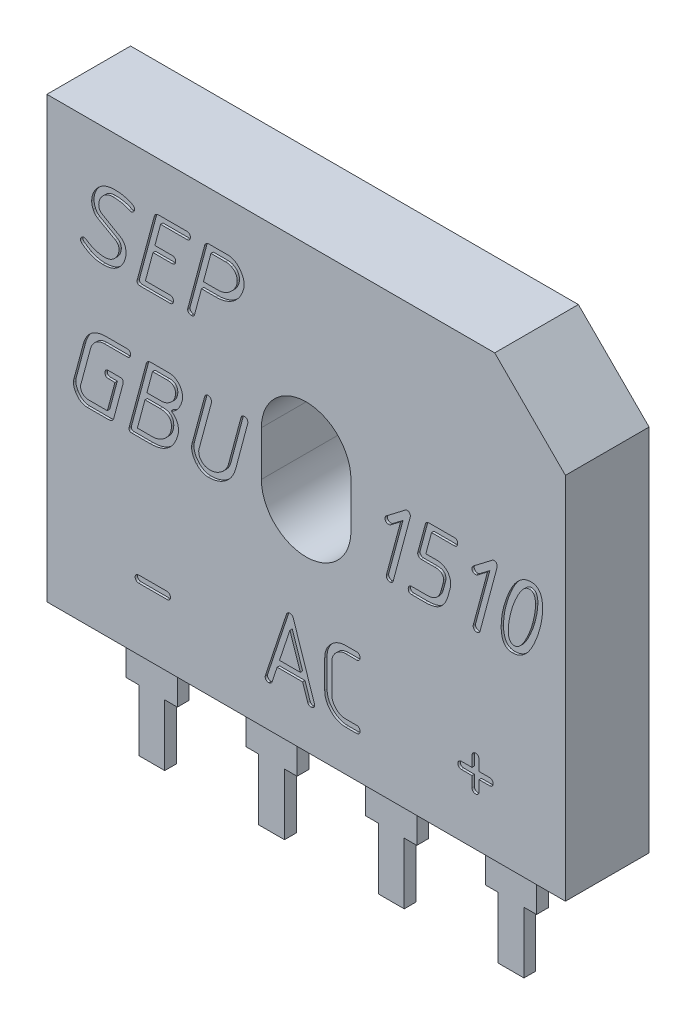
SolidWorks part; units mm, degrees
ref_plane "Front Plane" through (0, 0, 0) normal (0, 0, 1) x (1, 0, 0)
ref_plane "Top Plane" through (0, 0, 0) normal (0, 1, 0) x (1, 0, 0)
ref_plane "Right Plane" through (0, 0, 0) normal (1, 0, 0) x (0, 0, -1)
sketch "Sketch1" plane through (0, 0, 0) normal (0, 0, 1) x (1, 0, 0)
  line L0 (0, -402.7877) -> (0, 19736.5997) construction
  line L1 (-402.7877, 0) -> (19736.5997, 0) construction
  line L2 (8, 20.92) -> (11, 17.92)
  line L3 (-11, 2.27) -> (11, 2.27)
  line L4 (-11, 2.27) -> (-11, 20.92)
  line L5 (-11, 20.92) -> (8, 20.92)
  line L6 (11, 2.27) -> (11, 17.92)
  line L7 (-999.0375, 12.27) -> (49000.9625, 12.27) construction
  line L8 (-1.9, 13.22) -> (-1.9, 11.32)
  line L9 (1.9, 13.22) -> (1.9, 11.32)
  line L10 (-7.62, -1000) -> (-7.62, 49000) construction
  line L11 (-6.535, 2.27) -> (-6.535, 0.1)
  line L12 (-6.535, 0.1) -> (-7.07, 0.1)
  line L13 (-7.07, 0.1) -> (-7.07, -2.5)
  line L14 (-8.17, 0.1) -> (-8.17, -2.5)
  line L15 (-8.705, 0.1) -> (-8.17, 0.1)
  line L16 (-8.705, 2.27) -> (-8.705, 0.1)
  line L17 (-8.17, -2.5) -> (-7.07, -2.5)
  line L18 (-8.705, 2.27) -> (-6.535, 2.27)
  line L19 (-1.455, 2.27) -> (-1.455, 0.1)
  line L20 (-1.455, 0.1) -> (-1.99, 0.1)
  line L21 (-1.99, 0.1) -> (-1.99, -2.5)
  line L22 (-3.09, 0.1) -> (-3.09, -2.5)
  line L23 (-3.625, 0.1) -> (-3.09, 0.1)
  line L24 (-3.625, 2.27) -> (-3.625, 0.1)
  line L25 (-3.09, -2.5) -> (-1.99, -2.5)
  line L26 (-3.625, 2.27) -> (-1.455, 2.27)
  line L27 (3.625, 2.27) -> (3.625, 0.1)
  line L28 (3.625, 0.1) -> (3.09, 0.1)
  line L29 (3.09, 0.1) -> (3.09, -2.5)
  line L30 (1.99, 0.1) -> (1.99, -2.5)
  line L31 (1.455, 0.1) -> (1.99, 0.1)
  line L32 (1.455, 2.27) -> (1.455, 0.1)
  line L33 (1.99, -2.5) -> (3.09, -2.5)
  line L34 (1.455, 2.27) -> (3.625, 2.27)
  line L35 (8.705, 2.27) -> (8.705, 0.1)
  line L36 (8.705, 0.1) -> (8.17, 0.1)
  line L37 (8.17, 0.1) -> (8.17, -2.5)
  line L38 (7.07, 0.1) -> (7.07, -2.5)
  line L39 (6.535, 0.1) -> (7.07, 0.1)
  line L40 (6.535, 2.27) -> (6.535, 0.1)
  line L41 (7.07, -2.5) -> (8.17, -2.5)
  line L42 (6.535, 2.27) -> (8.705, 2.27)
  line L43 (-6.535, 2.27) -> (-1.455, 2.27) construction
  arc A0 (-1.9, 13.22) -> (1.9, 13.22) centre (0, 13.22) cw
  arc A1 (-1.9, 11.32) -> (1.9, 11.32) centre (0, 11.32) ccw
  point P6 (0, 2.27)
  dimension "D7" = 1.9
  dimension "D1" = 22
  dimension "D2" = 18.65
  dimension "D3" = 45
  dimension "D4" = 3
  dimension "D5" = 2.17
  dimension "D6" = 10
  dimension "D8" = 1.9
  dimension "D9" = 7.62
  dimension "D10" = 2.17
  dimension "D11" = 1.1
  dimension "D12" = 2.5
  dimension "D13" = 0.1
  dimension "D15" = 5.08
  dimension "D14" = 4
extrude "Boss-Extrude1" add sketch "Sketch1" along normal blind 1.32 contours L3 L6 L2 L5 L4 A1 L8 A0 L9 region at (9.2961, 19.2161, 0)
extrude "Boss-Extrude2" add sketch "Sketch1<3>" against normal blind 2.23 contours L3 L6 L2 L5 L4 A1 L8 A0 L9 region at (9.2961, 19.2161, 0)
sketch "Sketch1<3>" plane through (0, 0, 0) normal (0, 0, 1) x (1, 0, 0) same geometry as "Sketch1"
extrude "Boss-Extrude3" add sketch "Sketch1<4>" along normal mid plane 0.5 separate body contours L22 L25 L21 L20 L19 L3 L24 L23 | L38 L41 L37 L36 L35 L3 L40 L39 | L14 L17 L13 L12 L11 L18 L16 L15 | L30 L33 L29 L28 L27 L34 L32 L31 region at (7.62, 0.2838, 0) region at (-2.54, 0.2838, 0)
sketch "Sketch1<4>" plane through (0, 0, 0) normal (0, 0, 1) x (1, 0, 0) same geometry as "Sketch1"
sketch "Sketch2" plane through (0, 0, 1.32) normal (0, 0, 1) x (1, 0, 0)
  line L0 (-10.3451, 10.2759) -> (-2.79, 10.2759) construction
  line L1 (2.4452, 10.2759) -> (9.3732, 10.2759) construction
  line L2 (-10.0002, 15.8559) -> (-0.8778, 15.8559) construction
  line L4 (-9.2165, 4.0061) -> (9.8748, 4.0061) construction
  text T0 "<i>SEP</i>" font "ГОСТ тип А" height 3
  text T1 "GBU" font "ГОСТ тип А" height 3
  text T2 "1510" font "ГОСТ тип А" height 3
  text T3 "-  AC  +" font "OpenGost Type B TT" height 3
  point P8 (-8.2447, 4.1002)
  point P9 (-8.6522, 3.8807)
  point P10 (8.6522, 3.9748)
  point P11 (-7.9939, 3.9121)
  point P12 (0.3292, 4.0061)
  point P13 (-9.2165, 4.0061)
extrude "Cut-Extrude1" cut sketch "Sketch2" against normal blind 0.1
